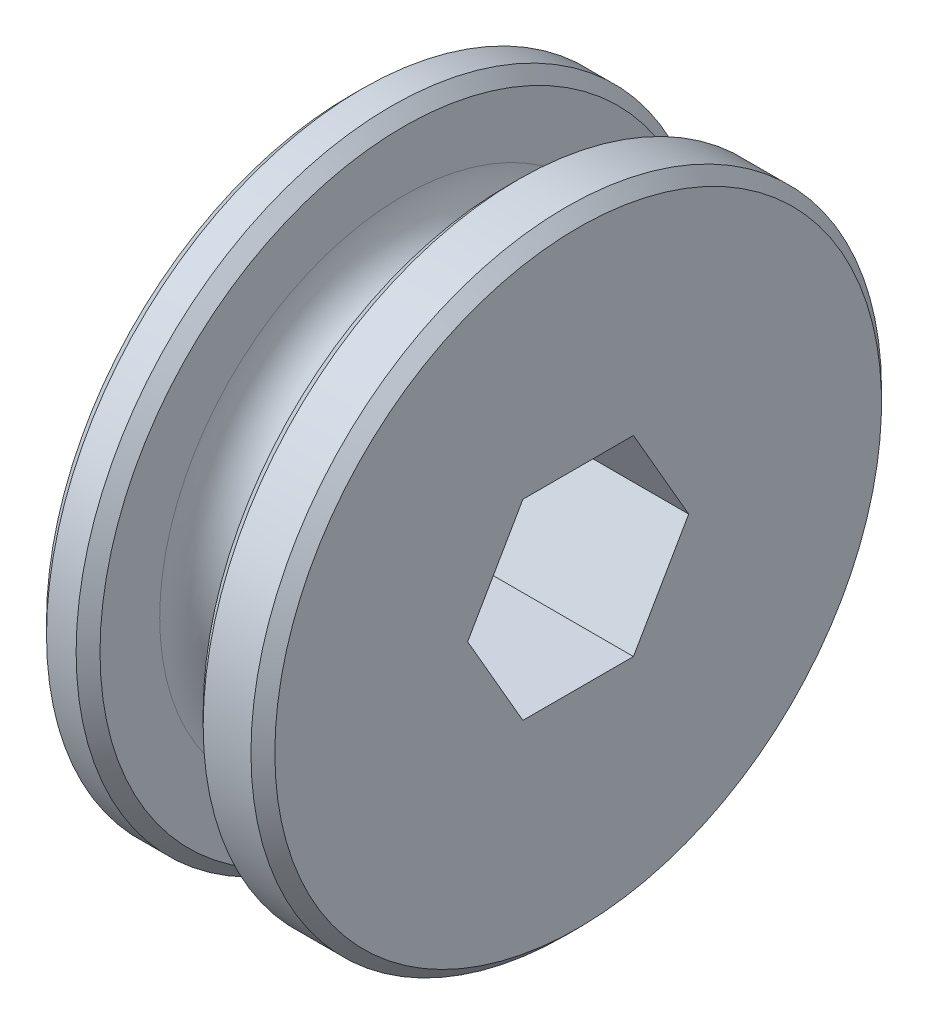
SolidWorks part; units mm, degrees
material "PET"
ref_plane "Front Plane" through (0, 0, 0) normal (0, 0, 1) x (1, 0, 0)
ref_plane "Top Plane" through (0, 0, 0) normal (0, 1, 0) x (1, 0, 0)
ref_plane "Right Plane" through (0, 0, 0) normal (1, 0, 0) x (0, 0, -1)
sketch "Sketch1" plane through (0, 0, 0) normal (0, 0, 1) x (1, 0, 0)
  line L0 (15.1765, 0) -> (0, 0)
  line L1 (0, 0) -> (15.1765, 0) construction
  line L2 (0, 0) -> (0, 20.955)
  line L3 (0, 20.955) -> (3.556, 20.955)
  line L4 (3.556, 16.1925) -> (3.556, 20.955)
  line L6 (10.414, 16.1925) -> (10.414, 20.955)
  line L7 (10.414, 20.955) -> (15.1765, 20.955)
  line L8 (15.1765, 0) -> (15.1765, 20.955)
  line L9 (6.985, 12.7635) -> (6.985, 0) construction
  arc A0 (3.556, 16.1925) -> (10.414, 16.1925) centre (6.985, 16.1925) ccw
  dimension "D1" = 3.429
  dimension "D2" = 4.7625
  dimension "D3" = 20.955
  dimension "D4" = 4.7625
  dimension "D5" = 3.556
  dimension "D7" = 12.7635
revolve "Revolve1" add sketch "Sketch1" angle 360 about L1 region at (7.7038, 9.1919, 0)
chamfer "Chamfer1" distance 0.7937 angle 45 1 edges at (0, 0, 20.955)
sketch "Sketch2" plane through (0, 0, 0) normal (-1, 0, 0) x (0, 0, 1)
  line L1 (3.6735, -6.3627) -> (7.347, 0)
  line L2 (7.347, 0) -> (3.6735, 6.3627)
  line L3 (3.6735, 6.3627) -> (-3.6735, 6.3627)
  line L4 (-3.6735, 6.3627) -> (-7.347, 0)
  line L5 (-7.347, 0) -> (-3.6735, -6.3627)
  line L6 (-3.6735, -6.3627) -> (3.6735, -6.3627)
  circle A0 centre (0, 0) radius 6.3627 construction
  dimension "D1" = 12.7254
extrude "Cut-Extrude1" cut sketch "Sketch2" against normal through all
chamfer "Chamfer2" distance 0.7937 angle 45 3 edges at (15.1765, 0, 20.955) (10.414, 0, 20.955) (3.556, 0, 20.955)
ref_plane "Plane1" through (6.985, 0, 0) normal (-1, 0, 0) x (0, 0, 1)
